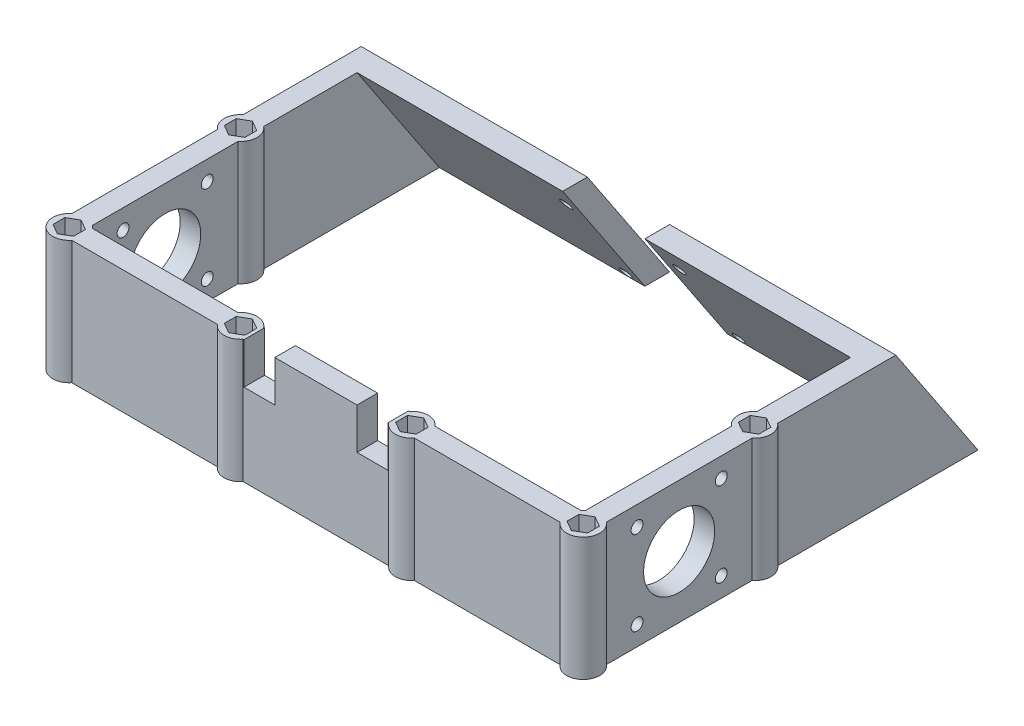
SolidWorks part; units mm, degrees
material "TPU"
ref_plane "Front Plane" through (0, 0, 0) normal (0, 0, 1) x (1, 0, 0)
ref_plane "Top Plane" through (0, 0, 0) normal (0, 1, 0) x (1, 0, 0)
ref_plane "Right Plane" through (0, 0, 0) normal (1, 0, 0) x (0, 0, -1)
sketch "Sketch4" plane through (0, 0, 0) normal (0, 1, 0) x (1, 0, 0)
  line L0 (0, 0) -> (0, -54.2428)
  line L1 (0, -114.3) -> (52.1261, -114.3) construction
  line L2 (165.1, -107.1594) -> (165.1, -62.1739)
  line L3 (165.1, 0) -> (158.75, 0)
  line L4 (158.75, 0) -> (158.75, -54.2428)
  line L7 (6.35, 0) -> (0, 0)
  line L8 (3.175, -111.125) -> (56.0917, -111.125) construction
  line L9 (56.0917, -111.125) -> (109.0083, -111.125) construction
  line L10 (109.0083, -111.125) -> (161.925, -111.125) construction
  line L11 (161.925, -111.125) -> (161.925, -58.2083) construction
  line L12 (6.35, -107.1594) -> (6.35, -62.1739)
  line L13 (6.35, -54.2428) -> (6.35, 0)
  line L14 (0, -62.1739) -> (0, -114.3) construction
  line L15 (0, -62.1739) -> (0, -107.1594)
  line L16 (7.1406, -114.3) -> (52.1261, -114.3)
  line L17 (52.1261, -107.95) -> (7.1406, -107.95)
  line L18 (60.0572, -114.3) -> (105.0428, -114.3) construction
  line L19 (60.0572, -114.3) -> (105.0428, -114.3)
  line L20 (105.0428, -107.95) -> (60.0572, -107.95)
  line L21 (112.9739, -114.3) -> (165.1, -114.3) construction
  line L22 (112.9739, -114.3) -> (157.9594, -114.3)
  line L23 (158.75, -62.1739) -> (158.75, -107.1594)
  line L24 (165.1, -54.2428) -> (165.1, 0)
  line L26 (157.9594, -107.95) -> (112.9739, -107.95)
  line L27 (0, -56.3752) -> (0, -60.0414)
  line L28 (0, -60.0414) -> (3.175, -61.8745)
  line L29 (3.175, -61.8745) -> (6.35, -60.0414)
  line L30 (6.35, -60.0414) -> (6.35, -56.3752)
  line L31 (6.35, -56.3752) -> (3.175, -54.5422)
  line L32 (3.175, -54.5422) -> (0, -56.3752)
  line L33 (3.175, -107.4588) -> (0, -109.2919)
  line L34 (0, -109.2919) -> (0, -112.9581)
  line L35 (0, -112.9581) -> (3.175, -114.7912)
  line L36 (3.175, -114.7912) -> (6.35, -112.9581)
  line L37 (6.35, -112.9581) -> (6.35, -109.2919)
  line L38 (6.35, -109.2919) -> (3.175, -107.4588)
  line L39 (56.0917, -107.4588) -> (52.9167, -109.2919)
  line L40 (52.9167, -109.2919) -> (52.9167, -112.9581)
  line L41 (52.9167, -112.9581) -> (56.0917, -114.7912)
  line L42 (56.0917, -114.7912) -> (59.2667, -112.9581)
  line L43 (59.2667, -112.9581) -> (59.2667, -109.2919)
  line L44 (59.2667, -109.2919) -> (56.0917, -107.4588)
  line L45 (109.0083, -107.4588) -> (105.8333, -109.2919)
  line L46 (105.8333, -109.2919) -> (105.8333, -112.9581)
  line L47 (105.8333, -112.9581) -> (109.0083, -114.7912)
  line L48 (109.0083, -114.7912) -> (112.1833, -112.9581)
  line L49 (112.1833, -112.9581) -> (112.1833, -109.2919)
  line L50 (112.1833, -109.2919) -> (109.0083, -107.4588)
  line L51 (161.925, -107.4588) -> (158.75, -109.2919)
  line L52 (158.75, -109.2919) -> (158.75, -112.9581)
  line L53 (158.75, -112.9581) -> (161.925, -114.7912)
  line L54 (161.925, -114.7912) -> (165.1, -112.9581)
  line L55 (165.1, -112.9581) -> (165.1, -109.2919)
  line L56 (165.1, -109.2919) -> (161.925, -107.4588)
  line L57 (161.925, -54.5422) -> (158.75, -56.3752)
  line L58 (158.75, -56.3752) -> (158.75, -60.0414)
  line L59 (158.75, -60.0414) -> (161.925, -61.8745)
  line L60 (161.925, -61.8745) -> (165.1, -60.0414)
  line L61 (165.1, -60.0414) -> (165.1, -56.3752)
  line L62 (165.1, -56.3752) -> (161.925, -54.5422)
  arc A6 (0, -54.2428) -> (0, -62.1739) centre (3.175, -58.2083) ccw
  arc A7 (6.35, -62.1739) -> (6.35, -54.2428) centre (3.175, -58.2083) ccw
  arc A8 (0, -107.1594) -> (7.1406, -114.3) centre (3.175, -111.125) ccw
  arc A9 (60.0572, -107.95) -> (52.1261, -107.95) centre (56.0917, -111.125) ccw
  arc A10 (52.1261, -114.3) -> (60.0572, -114.3) centre (56.0917, -111.125) ccw
  arc A11 (105.0428, -114.3) -> (112.9739, -114.3) centre (109.0083, -111.125) ccw
  arc A12 (112.9739, -107.95) -> (105.0428, -107.95) centre (109.0083, -111.125) ccw
  arc A13 (157.9594, -114.3) -> (165.1, -107.1594) centre (161.925, -111.125) ccw
  arc A14 (158.75, -54.2428) -> (158.75, -62.1739) centre (161.925, -58.2083) ccw
  arc A15 (165.1, -62.1739) -> (165.1, -54.2428) centre (161.925, -58.2083) ccw
  arc A16 (6.35, -107.1594) -> (7.1406, -107.95) centre (3.175, -111.125) cw
  arc A17 (158.75, -107.1594) -> (157.9594, -107.95) centre (161.925, -111.125) ccw
  circle A18 centre (3.175, -58.2083) radius 3.175 construction
  circle A19 centre (3.175, -111.125) radius 3.175 construction
  circle A20 centre (56.0917, -111.125) radius 3.175 construction
  circle A21 centre (109.0083, -111.125) radius 3.175 construction
  circle A22 centre (161.925, -111.125) radius 3.175 construction
  circle A23 centre (161.925, -58.2083) radius 3.175 construction
  point P30 (161.925, 0)
  point P51 (3.175, 0)
  dimension "D6" = 6.35
  dimension "D8" = 5.08
  dimension "D10" = 10.16
  dimension "D11" = 5.08
  dimension "D12" = 5.08
  dimension "D13" = 10.16
  dimension "D14" = 10.16
  dimension "D15" = 6.35
  dimension "D16" = 6.35
  dimension "D17" = 6.35
  dimension "D18" = 6.35
  dimension "D19" = 6.35
  dimension "D2" = 6.35
  dimension "D3" = 6.35
  dimension "D4" = 165.1
  dimension "D5" = 114.3
  dimension "D7" = 3.175
  dimension "D9" = 6.35
extrude "Boss-Extrude2" add sketch "Sketch4" along normal blind 38.1
chamfer "Chamfer2" distance 38.1 distance2 25.4 2 edges at (161.925, 38.1, 0) (3.175, 38.1, 0) first distance on face at (161.925, 19.05, 0) first distance on face at (3.175, 19.05, 0)
sketch "Sketch6" plane through (0, 0, 114.3) normal (0, 0, 1) x (1, 0, 0)
  line L0 (60.325, 38.1) -> (60.325, 25.4)
  line L1 (60.0572, 38.1) -> (105.0428, 38.1) construction
  line L2 (60.325, 25.4) -> (69.85, 25.4)
  line L3 (69.85, 25.4) -> (69.85, 38.1)
  line L4 (95.25, 38.1) -> (95.25, 25.4)
  line L5 (95.25, 25.4) -> (104.775, 25.4)
  line L6 (104.775, 25.4) -> (104.775, 38.1)
  line L7 (95.25, 38.1) -> (104.775, 38.1)
  line L8 (60.325, 38.1) -> (69.85, 38.1)
  line L9 (60.0572, 38.1) -> (60.325, 38.1) construction
  line L10 (104.775, 38.1) -> (105.0428, 38.1) construction
  dimension "D1" = 9.525
  dimension "D2" = 9.525
  dimension "D3" = 12.7
  dimension "D4" = 12.7
  dimension "D5" = 25.4
extrude "Cut-Extrude3" cut sketch "Sketch6" against normal through all
sketch "Sketch7" plane through (165.1, 0, 0) normal (1, 0, 0) x (0, 0, -1)
  line L0 (-71.6667, 32.05) -> (-97.6667, 6.05) construction
  line L1 (-71.6667, 32.05) -> (-71.6667, 6.05) construction
  line L2 (-71.6667, 6.05) -> (-97.6667, 6.05) construction
  line L3 (-97.6667, 6.05) -> (-97.6667, 32.05) construction
  line L4 (-97.6667, 32.05) -> (-71.6667, 32.05) construction
  line L6 (-116.205, 38.1) -> (-116.205, 0) construction
  line L7 (-116.205, 19.05) -> (-84.6667, 19.05) construction
  line L8 (-84.6667, 19.05) -> (-84.6667, 38.1) construction
  line L9 (-107.1594, 38.1) -> (-62.1739, 38.1) construction
  circle A0 centre (-84.6667, 19.05) radius 10.9855
  circle A1 centre (-71.6667, 32.05) radius 1.8415
  circle A2 centre (-71.6667, 6.05) radius 1.8415
  circle A3 centre (-97.6667, 6.05) radius 1.8415
  circle A4 centre (-97.6667, 32.05) radius 1.8415
  dimension "D2" = 21.971
  dimension "D3" = 3.683
  dimension "D1" = 26
extrude "Cut-Extrude4" cut sketch "Sketch7" against normal through all
sketch "Sketch8" plane through (0, 0, 0) normal (0, 0.5547, -0.8321) x (-1, 0, 0)
  line L0 (-165.1, 45.7905) -> (-95.25, 45.7905)
  line L1 (-95.25, 45.7905) -> (-95.25, 0)
  line L2 (-95.25, 0) -> (-165.1, 0)
  line L3 (-165.1, 0) -> (-165.1, 45.7905)
  line L4 (-69.85, 45.7905) -> (0, 45.7905)
  line L5 (0, 45.7905) -> (0, 0)
  line L6 (0, 0) -> (-69.85, 0)
  line L7 (-69.85, 0) -> (-69.85, 45.7905)
extrude "Boss-Extrude3" add sketch "Sketch8" along normal blind 6.35
sketch "Sketch9" plane through (165.1, 0, 0) normal (1, 0, 0) x (0, 0, -1)
  line L0 (-25.4, 38.1) -> (-17.7682, 38.1)
  line L1 (-20.1165, 41.6223) -> (5.2835, 3.5223) construction
  line L2 (-17.7682, 38.1) -> (-20.1165, 41.6223)
  line L3 (-20.1165, 41.6223) -> (-25.4, 38.1)
extrude "Cut-Extrude5" cut sketch "Sketch9" against normal through all and the other way through all
sketch "Sketch10" plane through (165.1, 0, 0) normal (1, 0, 0) x (0, 0, -1)
  line L0 (0, 0) -> (7.6318, 0)
  line L1 (7.6318, 0) -> (5.2835, 3.5223)
  line L2 (-17.7682, 38.1) -> (5.2835, 3.5223) construction
  line L3 (5.2835, 3.5223) -> (0, 0)
extrude "Boss-Extrude4" add sketch "Sketch10" against normal up to surface (69.85 mm away) up to face at (95.25, 19.9306, 9.4712)
sketch "Sketch11" plane through (0, 0, 0) normal (-1, 0, 0) x (0, 0, 1)
  line L0 (-5.2835, 3.5223) -> (-7.6318, 0)
  line L1 (-7.6318, 0) -> (0, 0)
  line L2 (0, 0) -> (-5.2835, 3.5223)
extrude "Boss-Extrude5" add sketch "Sketch11" against normal up to surface (69.85 mm away) up to face at (69.85, 19.9306, 9.4712)
sketch "Sketch12" plane through (0, 3.5223, -5.2835) normal (0, 0.5547, -0.8321) x (-1, 0, 0)
  line L0 (0, 41.5572) -> (-69.85, 41.5572) construction
  line L1 (-69.85, -4.2333) -> (0, -4.2333) construction
  line L2 (-69.85, 41.5572) -> (-69.85, -4.2333) construction
  line L3 (-95.25, -4.2333) -> (-95.25, 41.5572) construction
  circle A0 centre (-65.0875, 35.2072) radius 1.8288
  circle A1 centre (-65.0875, 2.1167) radius 1.8288
  circle A2 centre (-100.0125, 35.2072) radius 1.8288
  circle A3 centre (-100.0125, 2.1167) radius 1.8288
  point P14 (0, 0)
  point P15 (0, 0)
  point P16 (0, 0)
  point P17 (0, 0)
  point P18 (0, 0)
  dimension "D1" = 3.6576
  dimension "D2" = 3.6576
  dimension "D3" = 6.35
  dimension "D4" = 6.35
  dimension "D5" = 4.7625
  dimension "D6" = 4.7625
extrude "Cut-Extrude6" cut sketch "Sketch12" against normal through all
